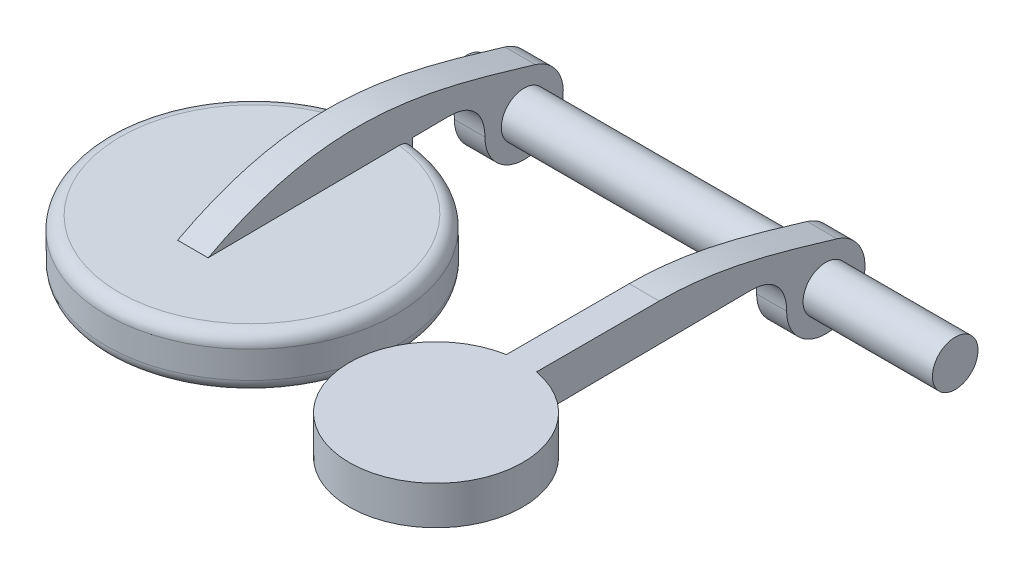
SolidWorks part; units mm, degrees
material "6061 Alloy"
ref_plane "Front Plane" through (0, 0, 0) normal (0, 0, 1) x (1, 0, 0)
ref_plane "Top Plane" through (0, 0, 0) normal (0, 1, 0) x (1, 0, 0)
ref_plane "Right Plane" through (0, 0, 0) normal (1, 0, 0) x (0, 0, -1)
sketch "Sketch2" plane through (0, 0, 0) normal (1, 0, 0) x (0, 0, -1)
  circle A0 centre (0, 0) radius 2.2352
  dimension "D1" = 4.4704
extrude "Boss-Extrude1" add sketch "Sketch2" along normal blind 47.9298
ref_plane "Plane1" through (2.6162, 0, 0) normal (1, 0, 0) x (0, 0, -1)
sketch "Sketch3" plane through (2.6162, 0, 0) normal (1, 0, 0) x (0, 0, -1)
  line L0 (-31.0134, 3.3159) -> (-7.476, 3.5361)
  arc A0 (-3.8481, 0) -> (1.1048, 3.6861) centre (0, 0) ccw
  arc A1 (1.1048, 3.6861) -> (-3.8481, 0) centre (0, 0) ccw construction
  spline S0 degree 3 poles (1.1048, 3.6861) (-9.328, 6.813) (-19.0654, 9.6909) (-31.0134, 3.3159) knots 0 0 0 0 1 1 1 1
  spline S1 degree 3 poles (-7.476, 3.5361) (-6.36, 3.5465) (-4.6187, 2.9341) (-3.8481, 1.1722) (-3.8481, 0) knots 0 0 0 0 0.485351 1 1 1 1
  point P1 (1.1048, 3.6861)
  point P3 (0, 0)
  point P7 (-4.8984, 2.6813)
  point P9 (0, 0)
  point P11 (0, 0)
  dimension "D2" = 31.0134
extrude "Boss-Extrude2" add sketch "Sketch3" along normal blind 2.9972
ref_plane "Plane2" through (0, 3.6057, 0.0337) normal (0, -1, -0.0094) x (-1, 0, 0)
sketch "Sketch4" plane through (0, 3.6057, 0.0337) normal (0, -1, -0.0094) x (-1, 0, 0)
  line L3 (-4.1148, -30.981) -> (-4.1148, -7.4426) construction
  line L4 (-5.6134, -30.981) -> (-2.6162, -30.981) construction
  line L5 (-5.6134, -7.4426) -> (-2.6162, -7.4426) construction
  circle A0 centre (-4.1148, -25.1781) radius 14.3129
  point P2 (0, 0)
  point P3 (0, 0)
  dimension "D1" = 28.6258
extrude "Boss-Extrude3" add sketch "Sketch4" along normal blind 5.207
fillet "Fillet1" radius 1.27 2 edges at (4.1148, 3.2364, 39.523) (4.1148, -1.7027, 10.8497)
ref_plane "Plane3" through (32.2834, 0, 0) normal (1, 0, 0) x (0, 0, -1)
sketch "Sketch5" plane through (32.2834, 0, 0) normal (1, 0, 0) x (0, 0, -1)
  line L0 (-16.3514, 7.1239) -> (-29.0514, 7.1239)
  line L1 (-29.0514, 7.1239) -> (-29.0514, 3.3343)
  line L2 (-31.0134, 3.3159) -> (-12.2548, 3.4914) construction
  line L4 (-29.0514, 3.3343) -> (-7.476, 3.5361)
  arc A0 (-3.8481, 0) -> (1.1048, 3.6861) centre (0, 0) ccw construction
  arc A1 (-3.8481, 0) -> (1.1048, 3.6861) centre (0, 0) ccw
  spline S0 degree 3 poles (-746.5573, -670.0783) (-132.7808, -93.9617) (84.7412, 111.7445) (-62.9847, -115.0659) (-998.9295, -98.9048) knots -9.758373 -9.758373 -9.758373 -9.758373 0.485351 9.639317 9.639317 9.639317 9.639317 only from (-7.476, 3.5361) to (-3.8481, 0) construction
  spline S1 degree 3 poles (494.2041, 873.6561) (-268.7358, -943.5627) (241.377, 970.2626) (-408.2266, -922.7879) knots -4.692692 -4.692692 -4.692692 -4.692692 4.732181 4.732181 4.732181 4.732181 only from (1.1048, 3.6861) to (-31.0134, 3.3159) construction
  spline S2 degree 3 poles (-7.476, 3.5361) (-6.36, 3.5465) (-4.6187, 2.9341) (-3.8481, 1.1722) (-3.8481, 0) knots 0 0 0 0 0.485351 1 1 1 1
  spline S3 degree 3 poles (1.1048, 3.6861) (-4.7616, 5.4444) (-10.4081, 7.1239) (-16.3514, 7.1239) knots 0 0 0 0 0.562302 0.562302 0.562302 0.562302
  spline S4 degree 3 poles (-29.0514, 4.29) (-29.699, 3.9926) (-30.3528, 3.6684) (-31.0134, 3.3159) knots 0.94471 0.94471 0.94471 0.94471 1 1 1 1 construction
  spline S5 degree 3 poles (-16.3514, 7.1239) (-20.3933, 7.1239) (-24.5724, 6.3471) (-29.0514, 4.29) knots 0.562302 0.562302 0.562302 0.562302 0.94471 0.94471 0.94471 0.94471 construction
  dimension "D1" = 12.7
extrude "Boss-Extrude4" add sketch "Sketch5" along normal blind 2.9464 contours L0 L1 L4 S2 A1 S3
ref_plane "Plane4" through (33.7566, 0, 0) normal (1, 0, 0) x (0, 0, -1)
sketch "Sketch6" plane through (33.7566, 0, 0) normal (1, 0, 0) x (0, 0, -1)
  line L0 (-29.0514, 3.3343) -> (-7.476, 3.5361) construction
  line L1 (-28.2777, 7.1239) -> (-36.7867, 7.1239)
  line L2 (-28.2777, 7.1239) -> (-28.2777, 3.3415)
  line L3 (-28.2777, 3.3415) -> (-36.7867, 3.3415)
  line L4 (-36.7867, 7.1239) -> (-36.7867, 3.3415)
  line L6 (-16.3514, 7.1239) -> (-29.0514, 7.1239) construction
  point P4 (0, 0)
  point P5 (0, 0)
  point P6 (0, 0)
  point P9 (-28.2777, 7.1239)
  dimension "D1" = 8.509
revolve "Revolve1" add sketch "Sketch6" angle 360 about L4
